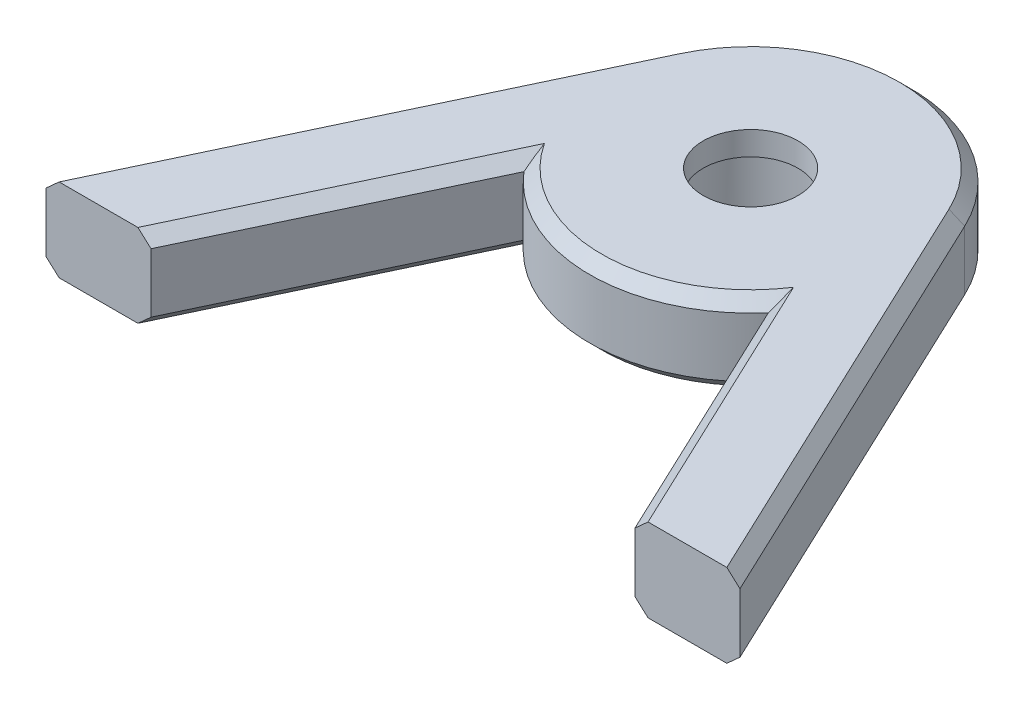
SolidWorks part; units mm, degrees
ref_plane "Front Plane" through (0, 0, 0) normal (0, 0, 1) x (1, 0, 0)
ref_plane "Top Plane" through (0, 0, 0) normal (0, 1, 0) x (1, 0, 0)
ref_plane "Right Plane" through (0, 0, 0) normal (1, 0, 0) x (0, 0, -1)
sketch "Sketch1" plane through (0, 0, 0) normal (0, 0, 1) x (1, 0, 0)
  line L0 (0, 0) -> (0, 24) construction
  line L1 (-30.2648, 5) -> (-19.3649, 5)
  line L2 (19.3649, 5) -> (30.2648, 5)
  circle A3 centre (0, 24) radius 2
  arc A7 (19.3649, 5) -> (-19.3649, 5) centre (0, 0) ccw
  circle A14 centre (0, 0) radius 24 construction
  circle A15 centre (20.7846, 12) radius 2
  circle A19 centre (-20.7846, 12) radius 2
  arc A20 (30.2648, 5) -> (-30.2648, 5) centre (0, 0) ccw
  circle A21 centre (-20.7846, -12) radius 2 [skipped]
  circle A22 centre (0, -24) radius 2 [skipped]
  circle A23 centre (20.7846, -12) radius 2 [skipped]
  point P16 (0, 0)
  dimension "D1" = 48
  dimension "D2" = 40
  dimension "D3" = 4
  dimension "D5" = 61.35
  dimension "D4" = 6
  dimension "D6" = 5
extrude "Boss-Extrude1" add sketch "Sketch1" along normal blind 5
chamfer "Chamfer6" distance 1 angle 65 2 edges at (0, 30.675, 0) (0, 20, 0) first distance on face at (0, 15.1688, 0)
sketch "Sketch4" plane through (0, 5, -5) normal (0, -1, 0) x (-1, 0, 0)
  line L0 (-19.3649, -10) -> (-30.2648, -10) construction
  line L4 (-30.2648, -7.1445) -> (-29.2507, -5) construction
  line L12 (-30.2648, -10) -> (-19.3649, -10)
  line L15 (-30.2648, -7.1445) -> (-30.2648, -10)
  line L16 (0, -2.3789) -> (0, 25.15) construction
  line L17 (-30.2648, -7.1445) -> (-12.2545, 30.9445)
  line L18 (-20.3961, -5) -> (-10.3043, 16.3426)
  line L20 (-30.2648, -10) -> (-30.2648, -7.1445) construction
  line L22 (0, -2.3789) -> (0, 34.8026) construction
  line L23 (0, -10) -> (0, -5) construction
  line L24 (-19.3649, -10) -> (19.3649, -10) construction
  line L25 (20.3961, -5) -> (-20.3961, -5) construction
  line L26 (-19.3649, -10) -> (-19.3649, -7.1445)
  line L27 (-20.3961, -5) -> (-19.3649, -7.1445)
  line L29 (30.2648, -7.1445) -> (29.2507, -5) construction
  line L30 (20.3961, -5) -> (19.3649, -7.1445)
  line L31 (19.3649, -10) -> (19.3649, -7.1445)
  line L32 (20.3961, -5) -> (10.3043, 16.3426)
  line L33 (30.2648, -7.1445) -> (12.2545, 30.9445)
  line L34 (30.2648, -7.1445) -> (30.2648, -10)
  line L35 (30.2648, -10) -> (19.3649, -10)
  circle A0 centre (0, 25.15) radius 5
  arc A1 (-10.3043, 16.3426) -> (10.3043, 16.3426) centre (0, 25.15) ccw
  arc A2 (12.2545, 30.9445) -> (-12.2545, 30.9445) centre (0, 25.15) ccw
  dimension "D1" = 10
  dimension "D3" = 35.15
extrude "Boss-Extrude4" add sketch "Sketch4" along normal blind 6
sketch "Sketch5" plane through (0, 5, 0) normal (0, 1, 0) x (1, 0, 0)
  line L6 (10.3043, 21.3426) -> (20.3961, 0)
  line L7 (20.3961, 0) -> (29.2507, 0)
  line L8 (29.2507, 0) -> (12.2545, 35.9445)
  line L9 (-12.2545, 35.9445) -> (-29.2507, 0)
  line L10 (-29.2507, 0) -> (-20.3961, 0)
  line L11 (-20.3961, 0) -> (-10.3043, 21.3426)
  line L12 (10.3043, 21.3426) -> (20.3961, 0)
  line L13 (20.3961, 0) -> (29.2507, 0)
  line L14 (29.2507, 0) -> (12.2545, 35.9445)
  line L15 (-12.2545, 35.9445) -> (-29.2507, 0)
  line L16 (-29.2507, 0) -> (-20.3961, 0)
  line L17 (-20.3961, 0) -> (-10.3043, 21.3426)
  arc A2 (12.2545, 35.9445) -> (-12.2545, 35.9445) centre (0, 30.15) ccw
  arc A3 (-10.3043, 21.3426) -> (10.3043, 21.3426) centre (0, 30.15) ccw
  arc A4 (12.2545, 35.9445) -> (-12.2545, 35.9445) centre (0, 30.15) ccw
  arc A5 (-10.3043, 21.3426) -> (10.3043, 21.3426) centre (0, 30.15) ccw
  circle A6 centre (0, 30.15) radius 4
  dimension "D2" = 8
  dimension "D1" = 0
extrude "Boss-Extrude5" add sketch "Sketch5" along normal blind 1 and the other way blind 1
chamfer "Chamfer8" distance 1 angle 45 6 edges at (-15.3502, 6, -10.6713) (0, 6, -16.5946) (15.3502, 6, -10.6713) (20.7526, 6, -17.9723) (0, 6, -43.7054) (-20.7526, 6, -17.9723)
chamfer "Chamfer9" distance 1 angle 45 12 edges at (-30.2648, -1, 3.5723) (-21.2596, -1, -16.9) (0, -1, -43.7054) (21.2596, -1, -16.9) (30.2648, -1, 3.5723) (-19.3649, -1, 3.5723) (-19.8805, -1, 1.0723) (19.3649, -1, 3.5723) (19.8805, -1, 1.0723) (-15.3502, -1, -10.6713) (0, -1, -16.5946) (15.3502, -1, -10.6713)
sketch "Sketch6" plane through (0, -1, 0) normal (0, -1, 0) x (1, 0, 0)
  circle A0 centre (0, -30.15) radius 6
  circle A1 centre (0, -30.15) radius 10
  dimension "D1" = 20
  dimension "D2" = 12
extrude "Cut-Extrude1" cut sketch "Sketch6" against normal blind 1
sketch "Sketch7" plane through (0, 0, 5) normal (0, 0, 1) x (1, 0, 0)
  circle A0 centre (0, 0) radius 71.5755
extrude "Cut-Extrude2" cut sketch "Sketch7" against normal up to surface (5 mm away) up to face at (-0.8303, 5.5, 0)
